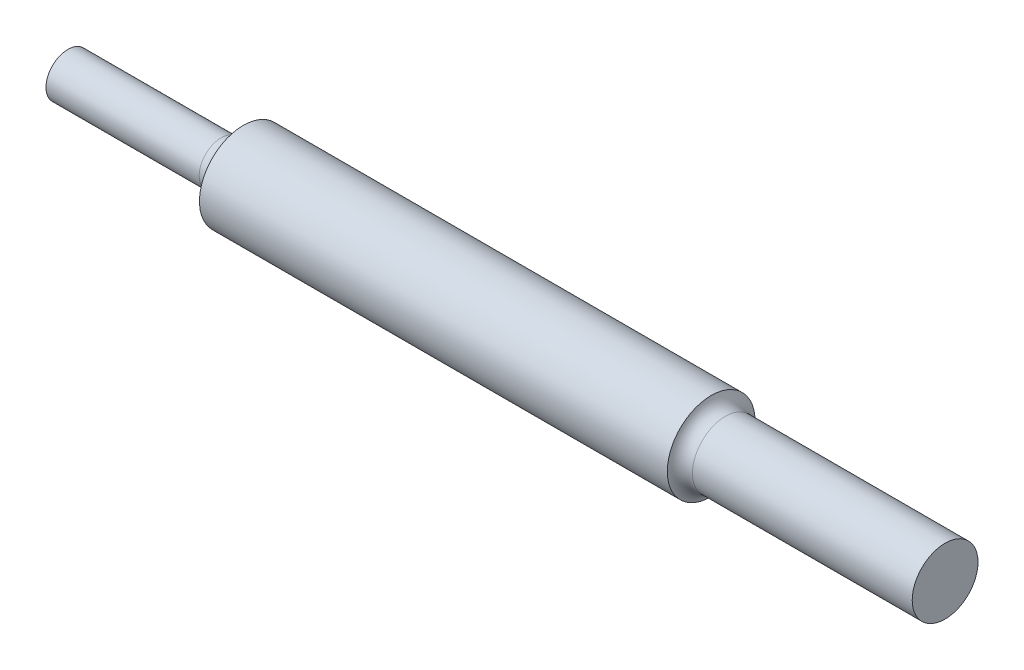
SolidWorks part; units mm, degrees
ref_plane "Front Plane" through (0, 0, 0) normal (0, 0, 1) x (1, 0, 0)
ref_plane "Top Plane" through (0, 0, 0) normal (0, 1, 0) x (1, 0, 0)
ref_plane "Right Plane" through (0, 0, 0) normal (1, 0, 0) x (0, 0, -1)
sketch "Sketch1" plane through (0, 0, 0) normal (1, 0, 0) x (0, 0, -1)
  circle A0 centre (0, 0) radius 19.05
  dimension "D1" = 38.1
extrude "Boss-Extrude1" add sketch "Sketch1" along normal blind 203.2
sketch "Sketch2" plane through (203.2, 0, 0) normal (1, 0, 0) x (0, 0, -1)
  circle A0 centre (0, 0) radius 14.2875
  dimension "D1" = 28.575
extrude "Boss-Extrude2" add sketch "Sketch2" along normal blind 101.6
sketch "Sketch3" plane through (0, 0, 0) normal (-1, 0, 0) x (0, 0, 1)
  circle A0 centre (0, 0) radius 9.525
  dimension "D1" = 19.05
extrude "Boss-Extrude3" add sketch "Sketch3" along normal blind 76.2
fillet "Fillet1" radius 9.652 1 edges at (0, 0, 9.525)
fillet "Fillet2" radius 6.35 1 edges at (203.2, 0, -14.2875)
